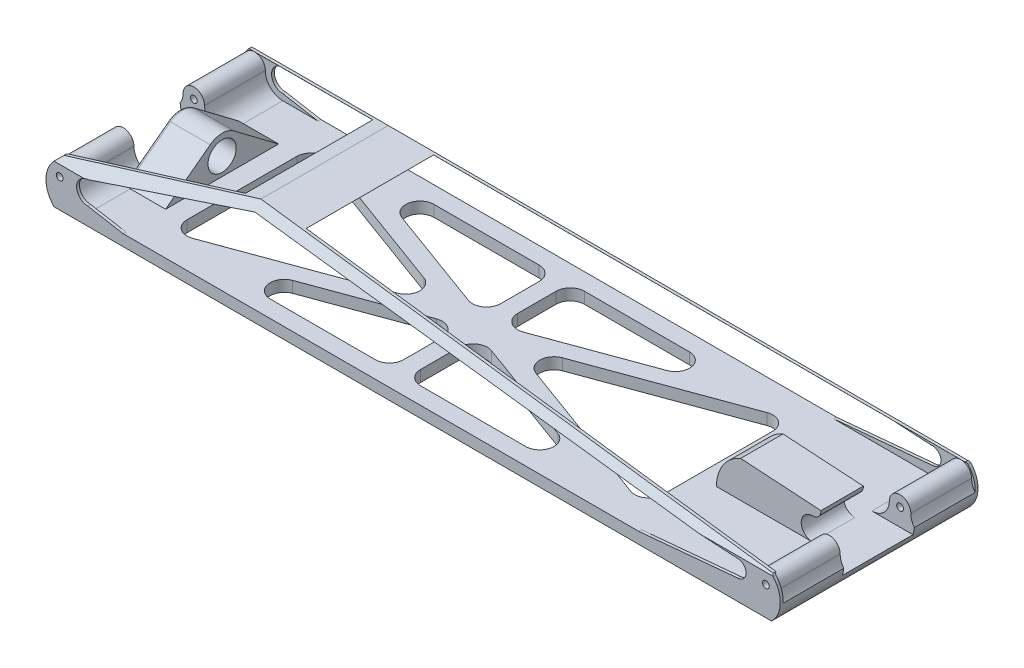
SolidWorks part; units mm, degrees
ref_plane "Front Plane" through (0, 0, 0) normal (0, 0, 1) x (1, 0, 0)
ref_plane "Top Plane" through (0, 0, 0) normal (0, 1, 0) x (1, 0, 0)
ref_plane "Right Plane" through (0, 0, 0) normal (1, 0, 0) x (0, 0, -1)
sketch "Sketch1" plane through (0, 0, 0) normal (0, 0, 1) x (1, 0, 0)
  line L1 (0, 0) -> (270, 0)
  line L2 (0, 0) -> (0, 4)
  line L3 (20, 4) -> (250, 4)
  line L4 (270, 0) -> (270, 4)
  circle A0 centre (10, 10.2) radius 1.2
  arc A1 (13.8, 10.2) -> (6.2, 10.2) centre (10, 10.2) ccw
  arc A2 (6.2, 10.2) -> (0, 4) centre (0, 10.2) cw
  arc A3 (13.8, 10.2) -> (20, 4) centre (20, 10.2) ccw
  circle A4 centre (260, 10.2) radius 1.2
  arc A5 (263.8, 10.2) -> (256.2, 10.2) centre (260, 10.2) ccw
  arc A6 (256.2, 10.2) -> (250, 4) centre (250, 10.2) cw
  arc A7 (263.8, 10.2) -> (270, 4) centre (270, 10.2) ccw
  dimension "D3" = 2.4
  dimension "D4" = 2.6
  dimension "D5" = 20
  dimension "D1" = 4
  dimension "D2" = 270
extrude "Boss-Extrude1" add sketch "Sketch1" along normal mid plane 70
sketch "Sketch2" plane through (0, 0, 0) normal (1, 0, 0) x (0, 0, -1)
  line L0 (35, 14) -> (-35, 14) construction
  line L1 (12.5, 4) -> (-12.5, 4)
  line L2 (12.5, 4) -> (12.5, 14)
  line L3 (12.5, 14) -> (-12.5, 14)
  line L4 (-12.5, 4) -> (-12.5, 14)
  line L5 (12.5, 4) -> (-12.5, 14) construction
  line L6 (12.5, 14) -> (-12.5, 4) construction
  line L7 (-35, 4) -> (35, 4) construction
  point P0 (0, 9)
  dimension "D1" = 25
extrude "Cut-Extrude1" cut sketch "Sketch2" along normal through all
sketch "Sketch3" plane through (0, 0, 0) normal (0, 0, 1) x (1, 0, 0)
  line L0 (250, 4) -> (20, 4) construction
  line L1 (249, 18) -> (229, 18)
  line L2 (249, 4) -> (215, 4)
  arc A0 (249, 4) -> (249, 12) centre (249, 8) cw
  arc A1 (249, 12) -> (249, 18) centre (249, 15) ccw
  arc A2 (229, 18) -> (215, 4) centre (229, 4) ccw
  dimension "D1" = 3
  dimension "D2" = 4
  dimension "D3" = 20
  dimension "D4" = 215
extrude "Boss-Extrude2" add sketch "Sketch3" along normal mid plane 15
sketch "Sketch4" plane through (0, 4, 0) normal (0, 1, 0) x (1, 0, 0)
  line L0 (0, -12.5) -> (0, 12.5) construction
  line L1 (17.5, -13) -> (0, -13)
  line L2 (17.5, -13) -> (17.5, 13)
  line L3 (17.5, 13) -> (0, 13)
  line L4 (0, -13) -> (0, 13)
  line L5 (17.5, -13) -> (0, 13) construction
  line L6 (17.5, 13) -> (0, -13) construction
  point P0 (8.75, 0)
  line M12 (20, 12.5) -> (0, 12.5)
  line M13 (0, 12.5) -> (0, -12.5)
  line M14 (0, -12.5) -> (20, -12.5)
  dimension "D1" = 17.5
  dimension "D2" = 26
extrude "Cut-Extrude2" cut sketch "Sketch4" against normal through all contours L2 M14 M12 M13 region at (8.75, 4, 0)
sketch "Sketch6" plane through (0, 0, 0) normal (1, 0, 0) x (0, 0, -1)
  line L0 (0, -1000) -> (0, 49000) construction
  line L1 (-35, 0) -> (35, 0) construction
  line L2 (-15.0134, 4) -> (-6.9951, 10.0391)
  line L3 (-4.2113, 15.8915) -> (-20, 4)
  line L4 (-20, 4) -> (-15.0134, 4)
  line L5 (-15.0134, 4) -> (15.0134, 4)
  line L6 (-12.5, 4) -> (12.5, 4) construction
  line L7 (20, 4) -> (15.0134, 4)
  line L8 (4.2113, 15.8915) -> (20, 4)
  line L9 (15.0134, 4) -> (6.9951, 10.0391)
  circle A0 centre (0, 10.3) radius 5
  arc A1 (4.2113, 15.8915) -> (-4.2113, 15.8915) centre (0, 10.3) ccw
  arc A2 (-6.9951, 10.0391) -> (-3.0512, 4) centre (0, 10.3) ccw
  arc A3 (3.0512, 4) -> (6.9951, 10.0391) centre (0, 10.3) ccw
  point P5 (0, 0)
  dimension "D1" = 5
  dimension "D2" = 2
  dimension "D3" = 3
  dimension "D4" = 10.3
  dimension "D5" = 20
extrude "Boss-Extrude3" add sketch "Sketch6" along normal blind 15 from offset 17.5 contours A2 L2 L5 | L5 L0 A0 A1 L3 L4 L2 A2 | L0 L5 A3 L9 L7 L8 A1 A0 | A3 L5 L9 region at (0, 9.3398, 8.2907) region at (0, 9.3398, -8.2907) region at (0, 5.8901, 8.8213) region at (0, 5.8901, -8.8213)
sketch "Sketch12" plane through (0, 4, 0) normal (0, 1, 0) x (1, 0, 0)
  line L0 (215, -35) -> (215, 35)
  line L1 (250, -35) -> (20, -35) construction
  line L2 (250, 35) -> (20, 35) construction
  line L4 (32.5, 35) -> (215, 35)
  line L5 (32.5, -35) -> (215, -35)
  line L6 (0, 0) -> (-7.094, 0) construction
  line L7 (120.75, -35) -> (126.75, -35)
  line L8 (120.75, -35) -> (120.75, 35)
  line L9 (120.75, 35) -> (126.75, 35)
  line L10 (126.75, -35) -> (126.75, 35)
  line L11 (120.75, -35) -> (126.75, 35) construction
  line L12 (120.75, 35) -> (126.75, -35) construction
  line L13 (213.5, -35) -> (126.75, -3.1953)
  line L14 (126.75, -3.1953) -> (126.75, 3.1953)
  line L15 (126.75, 3.1953) -> (215, -29.1594)
  line L16 (126.75, -3.1953) -> (215, 29.1594)
  line L17 (213.5, 35) -> (126.75, 3.1953)
  line L18 (123.75, -35) -> (123.75, 35) construction
  line L19 (34, 35) -> (120.75, 3.1953)
  line L20 (120.75, -3.1953) -> (32.5, 29.1594)
  line L21 (120.75, 3.1953) -> (32.5, -29.1594)
  line L22 (34, -35) -> (120.75, -3.1953)
  line L23 (50.3655, -29) -> (197.1345, -29)
  line L24 (50.3655, 29) -> (197.1345, 29)
  line L25 (39.5, -26.593) -> (39.5, 26.593)
  line L26 (208, -26.593) -> (208, 26.593)
  line L27 (32.5, -35) -> (32.5, 35)
  line L28 (32.5, -20) -> (32.5, 20) construction
  point P10 (123.75, 0)
  point P18 (123.75, -35)
  dimension "D1" = 6
  dimension "D2" = 6
  dimension "D3" = 7
  dimension "D4" = 1.5
  dimension "D5" = 5.8406
  dimension "D6" = 6
extrude "Cut-Extrude7" cut sketch "Sketch12" against normal through all contours L22 L23 L8 | L25 L21 L20 | L24 L19 L8 | L24 L10 L17 | L15 L26 L16 | L10 L23 L13 region at (183.8218, 4, 0) region at (150.2115, 4, 20.3984) region at (150.2115, 4, -20.3984) region at (97.2885, 4, 20.3984) region at (97.2885, 4, -20.3984) region at (63.6782, 4, 0)
fillet "Fillet8" radius 5 18 edges at (126.75, 2, 29) (120.75, 2, -3.1953) (50.3655, 2, -29) (50.3655, 2, 29) (39.5, 2, -26.593) (39.5, 2, 26.593) (208, 2, 26.593) (208, 2, -26.593) (135.4653, 2, 0) (126.75, 2, 3.1953) (126.75, 2, -3.1953) (126.75, 2, -29) (112.0347, 2, 0) (120.75, 2, -29) (120.75, 2, 29) (120.75, 2, 3.1953) (197.1345, 2, 29) (197.1345, 2, -29)
fillet "Fillet9" radius 1 3 edges at (17.5, 10.2089, -11.7562) (17.5, 10.2089, 11.7562) (17.5, 17.3, 0)
sketch "Sketch14" plane through (0, 0, 0) normal (1, 0, 0) x (0, 0, -1)
  line L0 (-35, 0) -> (-35, 14)
  line L1 (-35, 14) -> (-35, 10.2) construction
  line L2 (0, 0) -> (0, 26.547) construction
  line L3 (-35, 14) -> (-22.5402, 26.547)
  line L4 (22.5402, 26.547) -> (20.5509, 26.547)
  line L8 (0, 26.547) -> (0, 25.547)
  line L19 (-35, 0) -> (-34, 0)
  line L29 (-35, 0) -> (35, 0) construction
  line L30 (-34, 0) -> (-34, 14)
  line L31 (-12.5, 14) -> (-35, 14) construction
  line L32 (22.5402, 25.547) -> (-22.5402, 25.547)
  line L33 (-22.5402, 25.547) -> (-34, 14)
  line L34 (22.5402, 26.547) -> (-22.5402, 26.547)
  line L35 (22.5402, 25.547) -> (34, 14)
  line L36 (34, 0) -> (34, 14)
  line L37 (35, 0) -> (34, 0)
  line L38 (35, 14) -> (22.5402, 26.547)
  line L39 (35, 0) -> (35, 14)
extrude "Boss-Extrude4" add sketch "Sketch14" along normal through all contours L8 L4 L3 L0 | L4 L8 region at (0, 7, 34.5607) region at (0, 26.1077, -10.2754)
sketch "Sketch16" plane through (0, 0, 0) normal (0, 0, 1) x (1, 0, 0)
  line L0 (0, 14) -> (68.7925, 26.547)
  line L1 (270, 26.547) -> (0, 26.547) construction
  line L2 (68.7925, 26.547) -> (270, 14)
  line L3 (270, 14) -> (270, 26.547) construction
  line L4 (270, 14) -> (0, 14) construction
  line L5 (0, 14) -> (0, 26.547)
  line L6 (0, 26.547) -> (68.7925, 26.547)
  line L7 (270, 26.547) -> (68.7925, 26.547)
  line L8 (270, 14) -> (270, 26.547)
extrude "Cut-Extrude8" cut sketch "Sketch16" against normal through all both and the other way through all contours L6 L5 L0 | L2 L8 L7 region at (22.9308, 22.3646, 0) region at (202.9308, 22.3646, 0)
sketch "Sketch24" plane through (0, 0, 0) normal (0, 0, 1) x (1, 0, 0)
  line L0 (32.5, 4) -> (32.5, 16)
  line L1 (32.5, 16) -> (69.1855, 24.0012)
  line L2 (69.1855, 24.0012) -> (218.8635, 13.6566)
  line L5 (215, 4) -> (32.5, 4)
  arc A0 (218.8635, 13.6566) -> (215, 4) centre (229, 4) ccw
  arc A2 (223.5519, 16.8964) -> (215, 4) centre (229, 4) ccw construction
  point P3 (69.1855, 24.0012)
extrude "Cut-Extrude11" cut sketch "Sketch24" against normal through all both and the other way through all
sketch "Sketch19" plane through (0, 0, 12.5) normal (0, 0, -1) x (-1, 0, 0)
  circle A0 centre (-260, 10.2) radius 1.2
sketch "Sketch20" plane through (0, 0, 12.5) normal (0, 0, -1) x (-1, 0, 0)
extrude "Cut-Extrude9" cut sketch "Sketch19" against normal through all both and the other way through all
sketch "Sketch21" plane through (0, 0, -12.5) normal (0, 0, 1) x (1, 0, 0)
  circle A0 centre (10, 10.2) radius 1.2
extrude "Cut-Extrude10" cut sketch "Sketch21" against normal through all both and the other way through all
chamfer "Chamfer1" distance 8 angle 45 5 edges at (0, 14, -34.5) (270, 0, 0) (270, 14, -34.5) (270, 14, 34.5) (0, 14, 34.5) first distance on face at (0, 6, -27.1667) first distance on face at (71.875, 0, 0) first distance on face at (173.4054, 20.0235, 0) first distance on face at (0, 6, 27.1667)
chamfer "Chamfer2" distance 8 angle 45 2 edges at (0, 0, -23.75) (0, 0, 23.75)
sketch "Sketch25" plane through (0, 0, 35) normal (0, 0, 1) x (1, 0, 0)
  line L0 (20, 14.2) -> (69.1855, 24.0012)
  line L1 (20, 6.2) -> (32.5, 4)
  line L2 (69.1855, 24.0012) -> (32.5, 4)
  line L3 (250, 13.2) -> (69.1855, 24.0012)
  line L4 (250, 7.2) -> (215, 4)
  line L5 (69.1855, 24.0012) -> (215, 4)
  line L6 (266, 4) -> (266, 9.9834)
  line L7 (262, 0) -> (268.8052, 6.8052) construction
  line L8 (268.8052, 6.8052) -> (262.455, 14) construction
  line L10 (266, 9.9834) -> (269.9065, 9.9834)
  line L11 (266, 9.9834) -> (266, 4)
  line L12 (266, 4) -> (269.9065, 4)
  line L13 (269.9065, 9.9834) -> (269.9065, 4)
  arc A0 (20, 14.2) -> (20, 6.2) centre (20, 10.2) ccw
  arc A1 (250, 7.2) -> (250, 13.2) centre (250, 10.2) ccw
  circle A2 centre (0, 10.2) radius 6
  line M10 (262.455, 14) -> (213.8951, 14)
  line M11 (213.8951, 14) -> (218.8635, 13.6566)
  arc M12 (218.8635, 13.6566) -> (215, 4) centre (229, 4) ccw
  line M14 (32.5, 4) -> (32.5, 14)
  line M15 (32.5, 14) -> (8, 14)
extrude "Cut-Extrude13" cut sketch "Sketch25" against normal up to vertex (15 mm away) contours L0 A0 L2 M15 M14 | A0 L1 M15 M14 | L3 L5 M12 M11 M10 | L4 A1 L3 M10 M11 M12 region at (168.0221, 14.3875, 35) region at (43.5108, 14.8971, 35) region at (25.0022, 9.6459, 35) region at (232.7319, 9.6285, 35) up to point (32.5, 4, 20)
sketch "Sketch26" plane through (0, 0, -35) normal (0, 0, -1) x (-1, 0, 0)
  line L0 (-249.7012, 13.1851) -> (-69.1855, 24.0012)
  line L1 (-69.1855, 24.0012) -> (-20, 14.2)
  line L2 (-20, 6.2) -> (-32.5, 4)
  line L3 (-32.5, 4) -> (-69.1855, 24.0012)
  line L4 (-250, 7.2) -> (-215, 4)
  line L5 (-215, 4) -> (-69.1855, 24.0012)
  arc A1 (-249.7012, 13.1851) -> (-250, 7.2) centre (-250, 10.2) ccw
  arc A2 (-20, 6.2) -> (-20, 14.2) centre (-20, 10.2) ccw
  line M8 (-8, 14) -> (-32.5, 14)
  line M9 (-32.5, 14) -> (-32.5, 4)
  arc M11 (-215, 4) -> (-218.8635, 13.6566) centre (-229, 4) ccw
  line M12 (-218.8635, 13.6566) -> (-213.8951, 14)
  line M13 (-213.8951, 14) -> (-262.455, 14)
extrude "Cut-Extrude14" cut sketch "Sketch26" against normal blind 15 contours L2 A2 M8 M9 | A2 L1 L3 M8 M9 | L0 A1 L4 M11 M12 M13 | L5 L0 M11 M13 M12 region at (43.5108, 14.8971, -35) region at (232.7166, 9.6226, -35) region at (167.9843, 14.3787, -35) region at (25.0022, 9.6459, -35)
fillet "Fillet10" radius 10 3 edges at (268.8052, 6.8052, 34.5) (1, 7, 34.5) (1, 7, -34.5)
